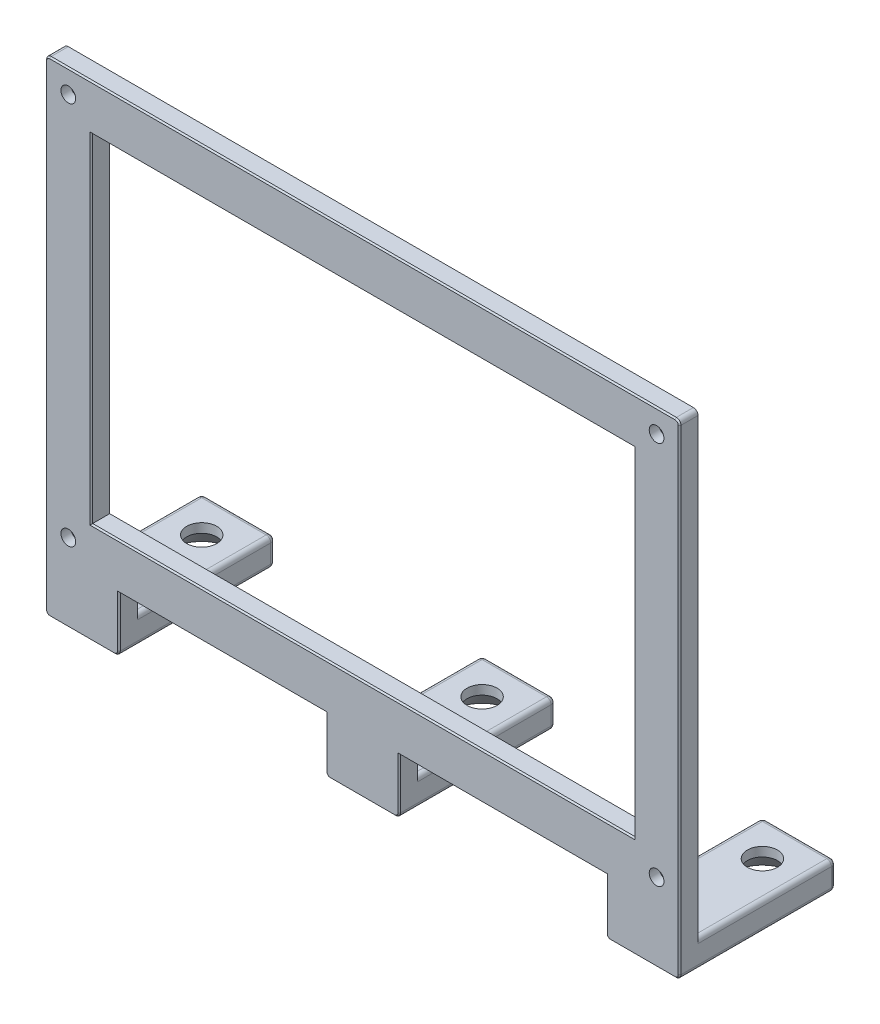
SolidWorks part; units mm, degrees
material "PE High Density"
ref_plane "Front Plane" through (0, 0, 0) normal (0, 0, 1) x (1, 0, 0)
ref_plane "Top Plane" through (0, 0, 0) normal (0, 1, 0) x (1, 0, 0)
ref_plane "Right Plane" through (0, 0, 0) normal (1, 0, 0) x (0, 0, -1)
sketch "Sketch1" plane through (0, 0, 0) normal (0, 0, 1) x (1, 0, 0)
  line L0 (-58.93, 45.21) -> (58.93, 45.21)
  line L1 (67.435, 45.21) -> (-67.435, 45.21) construction
  line L2 (67.435, 45.21) -> (67.435, -45.21) construction
  line L4 (-67.435, 45.21) -> (-67.435, -45.21) construction
  line L5 (0, -48.2) -> (0, 45.21) construction
  line L6 (67.435, 0) -> (-67.435, 0) construction
  line L7 (63.93, 40.21) -> (-63.93, 40.21) construction
  line L8 (63.93, 40.21) -> (63.93, -43.2) construction
  line L9 (63.93, -43.2) -> (-63.93, -43.2) construction
  line L10 (-63.93, 40.21) -> (-63.93, -43.2) construction
  line L11 (63.93, 40.21) -> (-63.93, -43.2) construction
  line L12 (63.93, -43.2) -> (-63.93, 40.21) construction
  line L14 (-58.93, 45.21) -> (-58.93, -48.2)
  line L15 (-58.93, -48.2) -> (-68.93, -48.2)
  line L16 (-68.93, 45.21) -> (-68.93, -48.2)
  line L17 (-58.93, 45.21) -> (-68.93, -48.2) construction
  line L18 (-58.93, -48.2) -> (-68.93, 45.21) construction
  line L19 (58.93, 45.21) -> (68.93, 45.21)
  line L20 (58.93, 45.21) -> (58.93, -48.2)
  line L21 (58.93, -48.2) -> (68.93, -48.2)
  line L22 (68.93, 45.21) -> (68.93, -48.2)
  line L23 (58.93, 45.21) -> (68.93, -48.2) construction
  line L24 (58.93, -48.2) -> (68.93, 45.21) construction
  line L25 (58.93, 35.21) -> (-58.93, 35.21)
  line L26 (0, 35.21) -> (0, 45.21) construction
  line L27 (-58.93, -48.2) -> (58.93, -48.2)
  line L28 (58.93, -38.2) -> (-58.93, -38.2)
  line L29 (0, -48.2) -> (0, -38.2) construction
  line L30 (-68.93, -54.2) -> (-52.93, -54.2)
  line L31 (-68.93, -48.2) -> (-52.93, -48.2)
  line L32 (-68.93, -48.2) -> (-68.93, -60.2)
  line L33 (-8, -48.2) -> (8, -48.2)
  line L34 (-8, -48.2) -> (-8, -60.2)
  line L35 (-8, -60.2) -> (8, -60.2)
  line L36 (8, -48.2) -> (8, -60.2)
  line L37 (-8, -48.2) -> (8, -60.2) construction
  line L38 (-8, -60.2) -> (8, -48.2) construction
  line L39 (-68.93, -60.2) -> (-52.93, -60.2)
  line L40 (-52.93, -48.2) -> (-52.93, -60.2)
  line L41 (68.93, -48.2) -> (52.93, -48.2)
  line L42 (68.93, -48.2) -> (68.93, -60.2)
  line L43 (68.93, -60.2) -> (52.93, -60.2)
  line L44 (52.93, -48.2) -> (52.93, -60.2)
  line L45 (-8, -54.2) -> (8, -54.2)
  line L46 (52.93, -54.2) -> (68.93, -54.2)
  line L47 (-68.93, 45.21) -> (-58.93, 45.21)
  circle A0 centre (-63.93, -43.2) radius 1.6
  circle A1 centre (-63.93, 40.21) radius 1.6
  circle A2 centre (63.93, 40.21) radius 1.6
  circle A3 centre (63.93, -43.2) radius 1.6
  point P0 (0, 0)
  point P4 (63.93, -1.495)
  point P6 (-63.93, -1.495)
  point P12 (0, -1.495)
  point P20 (68.93, -46.394)
  point P27 (0, 40.21)
  point P34 (0, -43.2)
  point P39 (0, -54.2)
  dimension "D5" = 3.2
  dimension "D1" = 83.41
  dimension "D2" = 127.86
  dimension "D3" = 90.42
  dimension "D4" = 134.87
  dimension "D6" = 12
  dimension "D7" = 16
  dimension "D8" = 10
extrude "Boss-Extrude1" add sketch "Sketch1" along normal blind 4 contours L16 L14 A1 A0 | L25 L20 L0 L14 | L22 L19 L20 A3 A2 | L22 L20 L21 | L16 L15 L14 | L36 L27 L34 | L36 L34 L35 | L20 L28 L14 L27 | L40 L27 L15 L32 L30 | L40 L30 L32 L39 | L44 L46 L42 L21 L27 | L46 L44 L43 L42 region at (0, 40.21, 0) region at (-63.93, -1.495, 0) region at (63.93, -1.495, 0) region at (0, -43.2, 0) region at (-60.93, -51.2, 0) region at (60.93, -51.2, 0) region at (-60.93, -57.2, 0) region at (60.93, -57.2, 0) region at (0, -51.2, 0) region at (0, -57.2, 0)
extrude "Boss-Extrude2" add sketch "Sketch1<3>" against normal blind 30 contours L40 L30 L32 L39 | L45 L34 L35 L36 | L46 L44 L43 L42 region at (-60.93, -57.2, 0) region at (60.93, -57.2, 0) region at (0, -57.2, 0)
sketch "Sketch1<3>" plane through (0, 0, 0) normal (0, 0, 1) x (1, 0, 0) same geometry as "Sketch1"
sketch "Sketch2" plane through (0, -60.2, 0) normal (0, -1, 0) x (1, 0, 0)
  line L0 (-60.93, -30) -> (-60.93, -22) construction
  line L1 (-68.93, -30) -> (-52.93, -30) construction
  line L3 (0, -22) -> (0, -30) construction
  line L5 (-8, -30) -> (8, -30) construction
  line L6 (60.93, -22) -> (60.93, -30) construction
  line L10 (68.93, -30) -> (52.93, -30) construction
  line L11 (-60.93, -22) -> (-52.93, -22) construction
  line L12 (-52.93, 4) -> (-52.93, -30) construction
  circle A0 centre (-60.93, -22) radius 3.2639
  circle A1 centre (0, -22) radius 3.2639
  circle A2 centre (60.93, -22) radius 3.2639
  dimension "D1" = 6.5278
extrude "Cut-Extrude1" cut sketch "Sketch2" against normal up to next
hole_wizard "CSK for 1/4 Flat Head Socket Cap Screw1" positions "Sketch3" profile "Sketch4" countersink size "1/4" standard "ANSI Inch" end condition through all
sketch "Sketch3" plane through (0, -60.2, 0) normal (0, -1, 0) x (-1, 0, 0)
  point P0 (60.93, 22)
  point P3 (0, 22)
  point P6 (-60.93, 22)
sketch "Sketch4" plane through (-60.93, -60.2, -22) normal (1, 0, 0) x (0, 0, -1)
  line L0 (0, 0) -> (0, 105.41)
  line L1 (0, 105.41) -> (3.2639, 105.41)
  line L2 (3.2639, 105.41) -> (3.2639, 4.0031)
  line L3 (3.2639, 4.0031) -> (6.7437, 0)
  line L5 (6.7437, 0) -> (0, 0)
  line L6 (-3.2639, 4.0031) -> (-6.7437, 0) construction
  line L11 (0, -6.35) -> (0, 107.95) construction
  dimension "Thru Hole Dia." = 6.5278
  dimension "Thru Hole Depth" = 105.41
  dimension "Near C'Sink Dia." = 13.4874
  dimension "Near C'Sink Angle" = 82
fillet "Fillet1" radius 1 26 edges at (-60.93, -54.2, -30) (-68.93, -57.2, -30) (-60.93, -60.2, -30) (-52.93, -57.2, -30) (-8, -57.2, -30) (0, -60.2, -30) (8, -57.2, -30) (0, -54.2, -30) (52.93, -57.2, -30) (60.93, -60.2, -30) (68.93, -57.2, -30) (60.93, -54.2, -30) (52.93, -54.2, -15) (-8, -54.2, -15) (-68.93, -54.2, -15) (-52.93, -54.2, -15) (8, -54.2, -15) (68.93, -54.2, -15) (68.93, -60.2, -13) (52.93, -60.2, -13) (8, -60.2, -13) (-8, -60.2, -13) (-68.93, -60.2, -13) (-52.93, -60.2, -13) (-68.93, 45.21, 2) (68.93, 45.21, 2)
hole_wizard "CSK for M3 SFHCS1" positions "Sketch5" profile "Sketch6" countersink size "M3" standard "ANSI Metric" end condition through all
sketch "Sketch5" plane through (0, 0, 0) normal (0, 0, -1) x (-1, 0, 0)
  point P0 (63.93, 40.21)
  point P3 (63.93, -43.2)
  point P6 (-63.93, -43.2)
  point P9 (-63.93, 40.21)
sketch "Sketch6" plane through (-63.93, 40.21, 0) normal (1, 0, 0) x (0, 1, 0)
  line L0 (0, 0) -> (0, 4)
  line L1 (0, 4) -> (1.6, 4)
  line L2 (1.6, 4) -> (1.6, 1.86)
  line L3 (1.6, 1.86) -> (3.46, 0)
  line L5 (3.46, 0) -> (0, 0)
  line L6 (-1.6, 1.86) -> (-3.46, 0) construction
  line L11 (0, -6.35) -> (0, 107.95) construction
  dimension "Thru Hole Dia." = 3.2
  dimension "Thru Hole Depth" = 4
  dimension "Near C'Sink Dia." = 6.92
  dimension "Near C'Sink Angle" = 90
chamfer "Chamfer1" distance 0.3 angle 45 24 edges at (0, -38.2, 4) (58.93, -1.495, 4) (-58.93, -1.495, 4) (0, 35.21, 4) (-8, -53.7, 4) (8, -53.7, 4) (-7.7071, -59.9071, 4) (7.7071, -59.9071, 4) (0, -60.2, 4) (30.465, -48.2, 4) (-30.465, -48.2, 4) (52.93, -53.7, 4) (53.2229, -59.9071, 4) (60.93, -60.2, 4) (68.6371, -59.9071, 4) (68.93, -7.495, 4) (68.6371, 44.9171, 4) (0, 45.21, 4) (-68.6371, 44.9171, 4) (-68.93, -7.495, 4) (-52.93, -53.7, 4) (-68.6371, -59.9071, 4) (-53.2229, -59.9071, 4) (-60.93, -60.2, 4)
